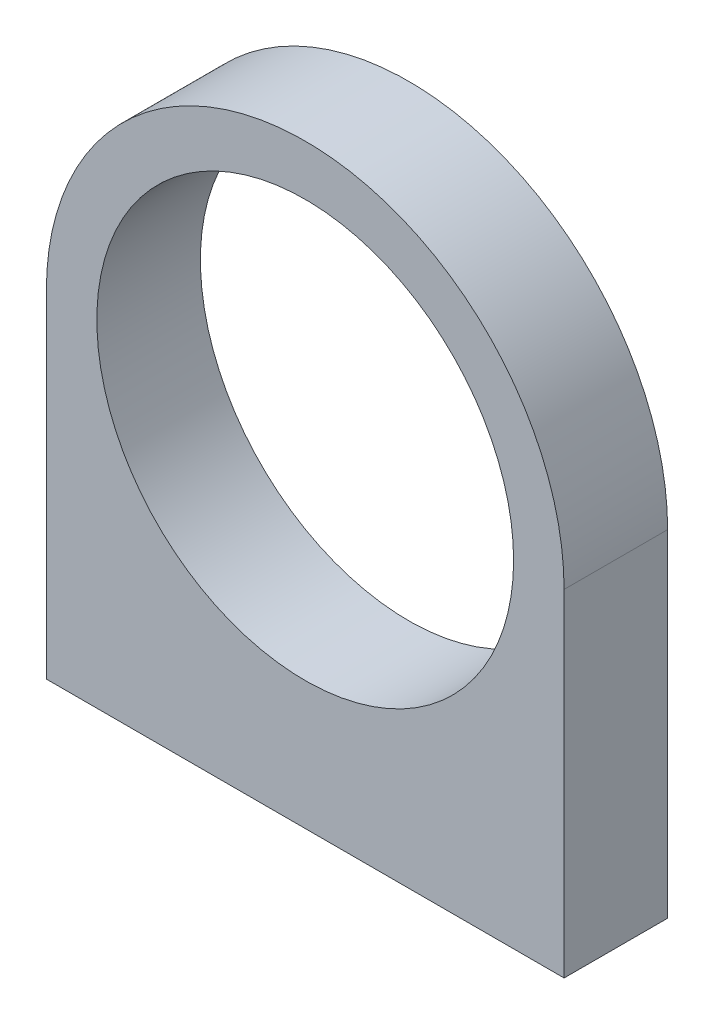
SolidWorks part; units mm, degrees
ref_plane "Plan de face" through (0, 0, 0) normal (0, 0, 1) x (1, 0, 0)
ref_plane "Plan de dessus" through (0, 0, 0) normal (0, 1, 0) x (1, 0, 0)
ref_plane "Plan de droite" through (0, 0, 0) normal (1, 0, 0) x (0, 0, -1)
sketch "Esquisse1" plane through (0, 0, 0) normal (0, 0, 1) x (1, 0, 0)
  line L1 (-20, 0) -> (20, 0) construction
  line L2 (-20, 0) -> (-20, -26)
  line L3 (-20, -26) -> (20, -26)
  line L4 (20, 0) -> (20, -26)
  circle A0 centre (0, 0) radius 20 construction
  arc A1 (-20, 0) -> (20, 0) centre (0, 0) cw
  circle A2 centre (0, 0) radius 16.1
  dimension "D1" = 40
  dimension "D3" = 32.2
  dimension "D2" = 26
extrude "Boss.-Extru.1" add sketch "Esquisse1" along normal blind 8
sketch "Esquisse2" plane through (0, -26, 0) normal (0, -1, 0) x (1, 0, 0)
  line L0 (-16, 4) -> (16, 4) construction
  line L1 (0, 0) -> (0, 8) construction
  line L2 (-20, 8) -> (20, 8) construction
  line L3 (-20, 8) -> (-20, 0) construction
  circle A0 centre (-16, 4) radius 1.5
  circle A1 centre (16, 4) radius 1.5
  point P8 (0, 4)
  point P9 (0, 4)
  dimension "D1" = 3
  dimension "D2" = 4
extrude "Enlèv. mat.-Extru.1" cut sketch "Esquisse2" against normal blind 15
